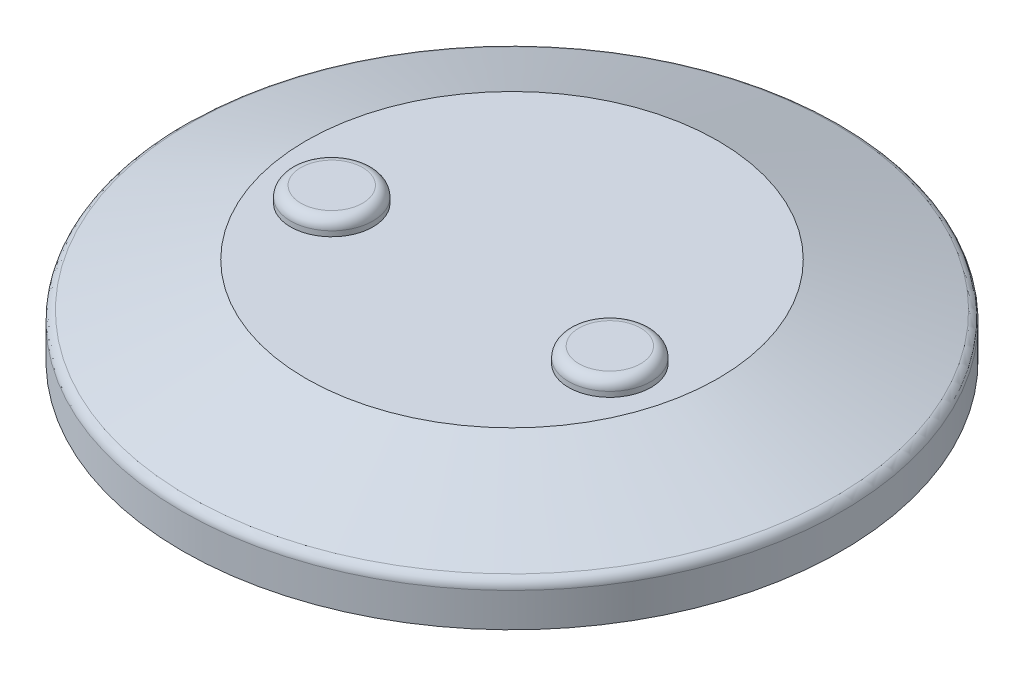
SolidWorks part; units mm, degrees
material "1060 Alloy"
ref_plane "Front Plane" through (0, 0, 0) normal (0, 0, 1) x (1, 0, 0)
ref_plane "Top Plane" through (0, 0, 0) normal (0, 1, 0) x (1, 0, 0)
ref_plane "Right Plane" through (0, 0, 0) normal (1, 0, 0) x (0, 0, -1)
sketch "Sketch1" plane through (0, 0, 0) normal (0, 1, 0) x (1, 0, 0)
  circle A0 centre (0, 0) radius 32
  dimension "D1" = 64
extrude "Boss-Extrude1" add sketch "Sketch1" along normal blind 4
sketch "Sketch2" plane through (0, 4, 0) normal (0, 1, 0) x (1, 0, 0)
  circle A0 centre (0, 0) radius 32 construction
  circle A1 centre (0, 0) radius 32
ref_plane "Plane1" through (0, 8.5, 0) normal (0, 1, 0) x (-1, 0, 0)
sketch "Sketch3" plane through (0, 8.5, 0) normal (0, 1, 0) x (-1, 0, 0)
  circle A0 centre (0, 0) radius 20
  dimension "D1" = 40
loft "Loft1" add profiles "Sketch3", "Sketch2" connector at (5.3272, 8.5, -19.2775) connector at (9.6903, 4, -30.4975)
fillet "Fillet1" radius 1 1 edges at (0, 4, 32)
sketch "Sketch4" plane through (0, 8.5, 0) normal (0, 1, 0) x (1, 0, 0)
  line L0 (0, 20) -> (0, -20) construction
  line L1 (-13.5, -4) -> (0, -4) construction
  line L2 (0, -4) -> (13.5, -4) construction
  circle A0 centre (0, 0) radius 20 construction
  circle A1 centre (-13.5, -4) radius 4
  circle A2 centre (13.5, -4) radius 4
  circle A3 centre (0, 0) radius 32 construction
  dimension "D1" = 8
  dimension "D2" = 27
  dimension "D3" = 4
extrude "Boss-Extrude2" add sketch "Sketch4" along normal blind 1.5
fillet "Fillet2" radius 1 2 edges at (-13.5, 10, 8) (13.5, 10, 8)
ref_plane "Plane2" through (0, 0, 4) normal (0, 0, 1) x (1, 0, 0)
ref_axis "Axis2" through (0, 9.975, 4) along (0, -1, 0)
sketch "Sketch5" plane through (0, 8.5, 0) normal (0, 1, 0) x (1, 0, 0)
  line L0 (0, -4) -> (-19.6157, -7.9018) construction
  line L1 (0, -4) -> (7.6537, 14.4776) construction
  line L2 (0, -4) -> (-20, -4) construction
  line L3 (0, -4) -> (0, 16) construction
  arc A0 (7.6537, 14.4776) -> (-19.6157, -7.9018) centre (0, -4) ccw
  dimension "D3" = 20
  dimension "D1" = 11.25
  dimension "D2" = 22.5
